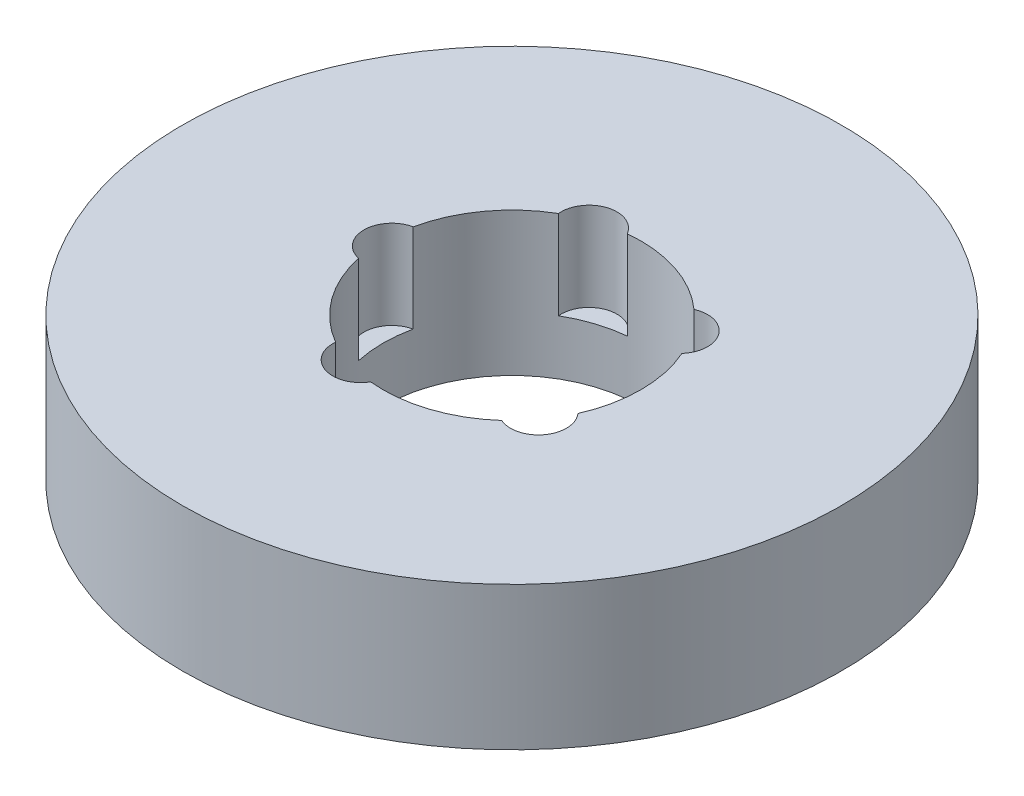
SolidWorks part; units mm, degrees
ref_plane "Front Plane" through (0, 0, 0) normal (0, 0, 1) x (1, 0, 0)
ref_plane "Top Plane" through (0, 0, 0) normal (0, 1, 0) x (1, 0, 0)
ref_plane "Right Plane" through (0, 0, 0) normal (1, 0, 0) x (0, 0, -1)
sketch "Sketch1" plane through (0, 0, 0) normal (0, 1, 0) x (1, 0, 0)
  circle A0 centre (0, 0) radius 57.5
  dimension "FLANGE_OD" = 115
extrude "Boss-Extrude1" add sketch "Sketch1" along normal blind 25
sketch "Sketch2" plane through (0, 0, 0) normal (0, 1, 0) x (1, 0, 0)
  circle A0 centre (0, 0) radius 22.5
  dimension "BORE_D" = 45
extrude "Cut-Extrude1" cut sketch "Sketch2" along normal through all
sketch "Sketch3" plane through (0, 25, 0) normal (0, 1, 0) x (1, 0, 0)
  circle A0 centre (0, 0) radius 20.9481 construction
  circle A1 centre (-20.9481, 0) radius 4.8755
  dimension "BOLT_D" = 9.751
  dimension "BOLT_PCD" = 41.8963
extrude "Cut-Extrude2" cut sketch "Sketch3" against normal blind 15.4548
pattern_circular "CirPattern1" count 5 over 360 about axis through (0, 0, 0) along (0, 1, 0) of "Cut-Extrude2"
